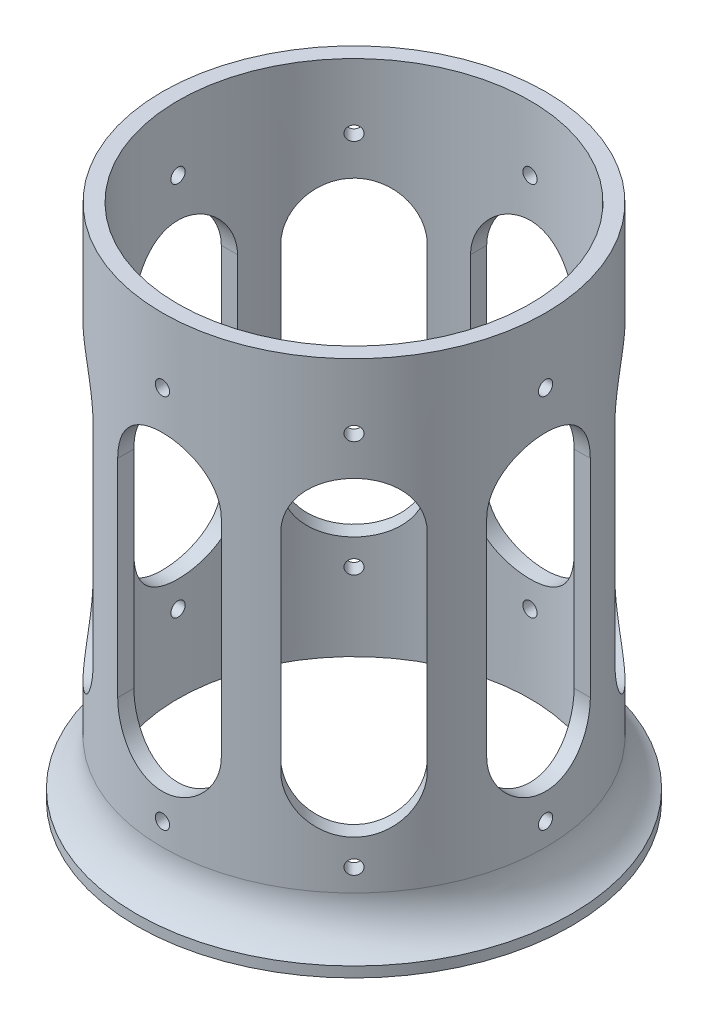
SolidWorks part; units mm, degrees
ref_plane "Front Plane" through (0, 0, 0) normal (0, 0, 1) x (1, 0, 0)
ref_plane "Top Plane" through (0, 0, 0) normal (0, 1, 0) x (1, 0, 0)
ref_plane "Right Plane" through (0, 0, 0) normal (1, 0, 0) x (0, 0, -1)
sketch "Body tube profile" plane through (0, 0, 0) normal (0, 1, 0) x (1, 0, 0)
  circle A0 centre (0, 0) radius 34
  dimension "D1" = 68
sketch "Sketch2" plane through (0, 0, 0) normal (0, 1, 0) x (1, 0, 0)
  circle A0 centre (0, 0) radius 34 construction
  circle A1 centre (0, 0) radius 34
  circle A2 centre (0, 0) radius 37
  dimension "D1" = 3
extrude "Main extrude" add sketch "Sketch2" along normal blind 100
sketch "Sketch3" plane through (0, 0, 0) normal (0, 0, 1) x (1, 0, 0)
  line L0 (-37, 0) -> (37, 0) construction
  line L1 (37, 100) -> (-37, 100) construction
  circle A0 centre (0, 15) radius 1.375
  circle A1 centre (0, 87.5) radius 1.375
  dimension "D1" = 2.75
  dimension "D3" = 2.75
  dimension "D2" = 15
  dimension "D4" = 12.5
extrude "Screwhole" cut sketch "Sketch3" along normal blind 100
sketch "Sketch4" plane through (0, 0, 0) normal (0, 0, 1) x (1, 0, 0)
  line L0 (0, 70) -> (0, 30) construction
  line L1 (10, 70) -> (10, 30)
  line L2 (-10, 70) -> (-10, 30)
  arc A0 (10, 70) -> (-10, 70) centre (0, 70) ccw
  arc A1 (-10, 30) -> (10, 30) centre (0, 30) ccw
  point P3 (0, 50)
  dimension "D3" = 10
  dimension "D1" = 50
  dimension "D2" = 40
extrude "Weight reduction" cut sketch "Sketch4" along normal blind 100
pattern_circular "Screwhole pattern" count 8 over 360 about axis through (0, 0, 0) along (0, 1, 0) of "Screwhole", "Weight reduction"
sketch "Sketch5" plane through (0, 0, 0) normal (0, -1, 0) x (1, 0, 0)
  circle A1 centre (0, 0) radius 37
  circle A2 centre (0, 0) radius 37 construction
  circle A3 centre (0, 0) radius 34 construction
  circle A27 centre (0, 0) radius 42
  circle A40 centre (0, 0) radius 34
  point P63 (0, 0)
  dimension "D1" = 0
  dimension "D7" = 5
extrude "Plate for better adhesion" add sketch "Sketch5" against normal blind 2
fillet "Fillet1" radius 10 1 edges at (0, 2, -37)
